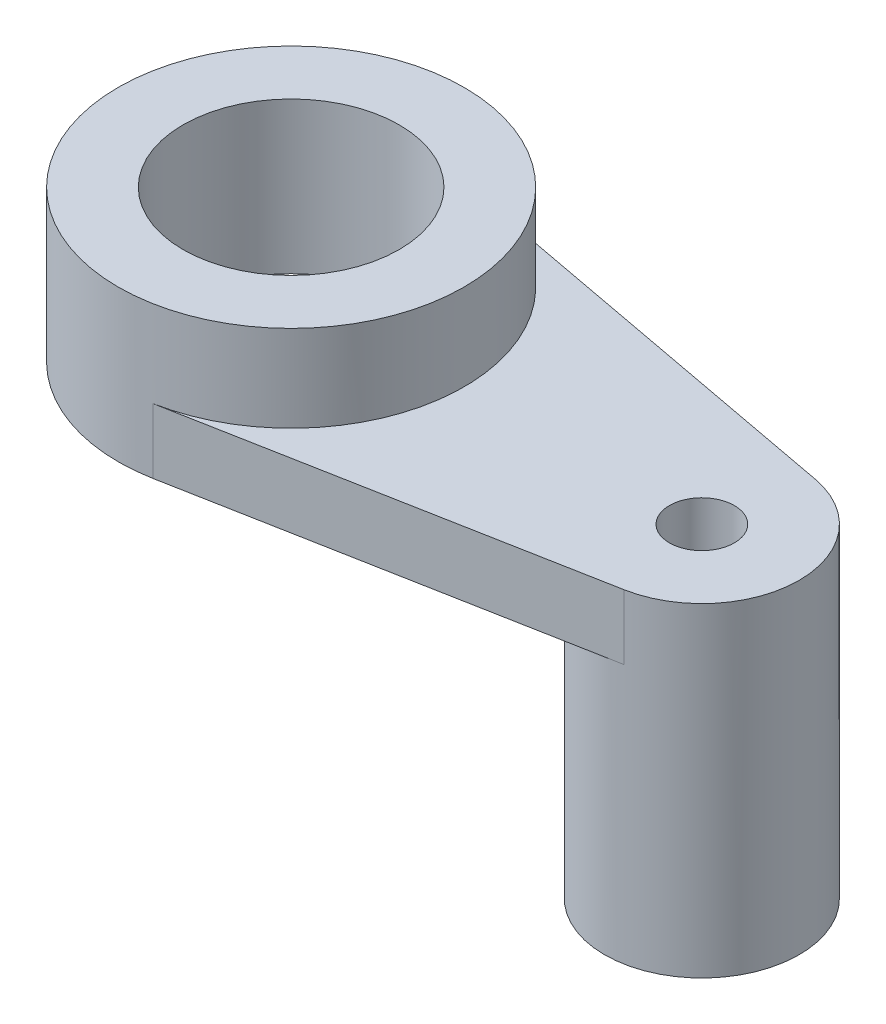
SolidWorks part; units mm, degrees
material "Galvanized Steel"
ref_plane "Front Plane" through (0, 0, 0) normal (0, 0, 1) x (1, 0, 0)
ref_plane "Top Plane" through (0, 0, 0) normal (0, 1, 0) x (1, 0, 0)
ref_plane "Right Plane" through (0, 0, 0) normal (1, 0, 0) x (0, 0, -1)
sketch "Sketch1" plane through (0, 0, 0) normal (0, 1, 0) x (1, 0, 0)
  line L0 (39.6579, 8.846) -> (2.9474, 15.7262)
  line L1 (2.9474, -15.7262) -> (39.6579, -8.846)
  circle A0 centre (0, 0) radius 10
  circle A1 centre (38, 0) radius 3
  arc A2 (2.9474, 15.7262) -> (2.9474, -15.7262) centre (0, 0) ccw
  arc A3 (39.6579, -8.846) -> (39.6579, 8.846) centre (38, 0) ccw
  circle A4 centre (0, 0) radius 16
  circle A5 centre (38, 0) radius 9
  dimension "D1" = 6
  dimension "D3" = 6
  dimension "D4" = 20
  dimension "D5" = 6
  dimension "D2" = 38
extrude "Boss-Extrude1" add sketch "Sketch1" along normal blind 6 contours A2 A4 A0 | A4 L1 A3 L0 A1 | A3 A5 A1 region at (21.925, 0, 0) region at (44.7295, 0, -5.5854) region at (11.9635, 0, -9.9296)
extrude "Boss-Extrude2" add sketch "Sketch1<3>" along normal blind 14 contours A2 A4 A0 region at (11.9635, 0, -9.9296)
sketch "Sketch1<3>" plane through (0, 0, 0) normal (0, 1, 0) x (1, 0, 0) same geometry as "Sketch1"
extrude "Boss-Extrude3" add sketch "Sketch1<4>" against normal blind 24 contours A3 A5 A1 region at (44.7295, 0, -5.5854)
sketch "Sketch1<4>" plane through (0, 0, 0) normal (0, 1, 0) x (1, 0, 0) same geometry as "Sketch1"
